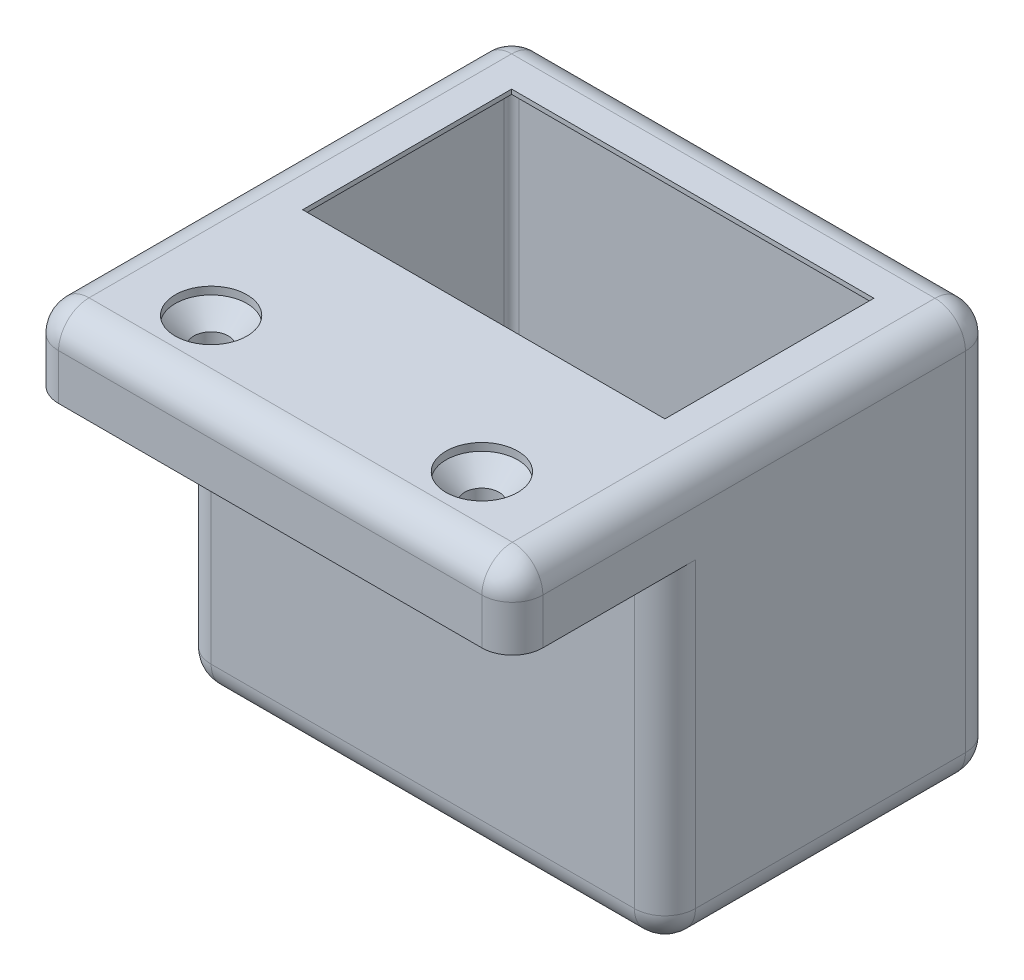
SolidWorks part; units mm, degrees
ref_plane "Front Plane" through (0, 0, 0) normal (0, 0, 1) x (1, 0, 0)
ref_plane "Top Plane" through (0, 0, 0) normal (0, 1, 0) x (1, 0, 0)
ref_plane "Right Plane" through (0, 0, 0) normal (1, 0, 0) x (0, 0, -1)
sketch "Profile Sketch" plane through (0, 0, 0) normal (1, 0, 0) x (0, 0, -1)
  line L0 (0, 0) -> (0, 43.6)
  line L1 (0, 43.6) -> (-20, 43.6)
  line L2 (-20, 43.6) -> (-20, 53.6)
  line L3 (-20, 53.6) -> (43.4, 53.6)
  line L4 (43.4, 53.6) -> (43.4, 0)
  line L5 (43.4, 0) -> (0, 0)
  dimension "D1" = 63.4
  dimension "D2" = 10
  dimension "D3" = 43.4
  dimension "D4" = 53.6
extrude "Profile Extrude" add sketch "Profile Sketch" along normal mid plane 63.5
sketch "Interior Sketch" plane through (0, 0, 0) normal (0, -1, 0) x (1, 0, 0)
  line L8 (-28.75, -3) -> (-28.75, -40.4)
  line L9 (-28.75, -40.4) -> (28.75, -40.4)
  line L10 (28.75, -40.4) -> (28.75, -3)
  line L11 (28.75, -3) -> (-28.75, -3)
  line L12 (-28.75, -3) -> (-28.75, -40.4)
  line L13 (-28.75, -40.4) -> (28.75, -40.4)
  line L14 (28.75, -40.4) -> (28.75, -3)
  line L15 (28.75, -3) -> (-28.75, -3)
  dimension "D1" = 3
extrude "Interior Cut" cut sketch "Interior Sketch" against normal offset from surface (50 mm away) 0.6 from offset 3 up to face at (0, 53.6, -11.7) offset against normal yes
sketch "Opening Sketch" plane through (0, 53.6, 0) normal (0, 1, 0) x (1, 0, 0)
  line L8 (-23.75, 8) -> (23.75, 8)
  line L9 (-23.75, 35.4) -> (-23.75, 8)
  line L10 (23.75, 35.4) -> (-23.75, 35.4)
  line L11 (23.75, 8) -> (23.75, 35.4)
  line L12 (-23.75, 8) -> (23.75, 8)
  line L13 (-23.75, 35.4) -> (-23.75, 8)
  line L14 (23.75, 35.4) -> (-23.75, 35.4)
  line L15 (23.75, 8) -> (23.75, 35.4)
  dimension "D1" = 5
extrude "Opening Cut" cut sketch "Opening Sketch" against normal up to next
chamfer "Inside Top Chamfer" distance 5 angle 45 4 edges at (28.75, 53, -21.7) (0, 53, -40.4) (-28.75, 53, -21.7) (0, 53, -3)
fillet "Inside Fillets" radius 1 4 edges at (-28.75, 25.5, -3) (28.75, 25.5, -3) (28.75, 25.5, -40.4) (-28.75, 25.5, -40.4)
sketch "Wire Outlet Cut Sketch" plane through (0, 0, 0) normal (0, -1, 0) x (1, 0, 0)
  line L0 (-31.75, -43.4) -> (31.75, 0) construction
  circle A0 centre (0, -21.7) radius 9.5
  dimension "D1" = 19
extrude "Wire Outlet Cut" cut sketch "Wire Outlet Cut Sketch" against normal up to next
fillet "Wire Outlet Fillet" 2 edges at (0, 0, -31.2) (0, 3, -31.2) type full round first side face at (0, 0, -31.2) second side face at (0, 3, -31.2) middle face at (0, 0, -31.2)
fillet "Top Fillets" radius 4 14 edges at (0, 0, 0) (31.75, 0, -21.7) (0, 0, -43.4) (-31.75, 0, -21.7) (-31.75, 26.8, -43.4) (0, 53.6, -43.4) (31.75, 26.8, -43.4) (-31.75, 21.8, 0) (31.75, 21.8, 0) (-31.75, 53.6, -11.7) (-31.75, 48.6, 20) (0, 53.6, 20) (31.75, 53.6, -11.7) (31.75, 48.6, 20)
sketch "Mounting Hole Layout Sketch" plane through (0, 53.6, 0) normal (0, 1, 0) x (1, 0, 0)
  line L0 (0, 0) -> (0, -27.8287) construction
  line L1 (27.75, -20) -> (-27.75, -20) construction
  point P3 (-17.75, -10)
  point P4 (17.75, -10)
  dimension "D1" = 35.5
  dimension "D2" = 10
hole_wizard "M4 Mounting Screws" positions "M4 Mounting Screws Position Sketch" profile "M4 Mounting Screws Profile Sketch" countersink size "M4" standard "ANSI Metric" end condition up to next
sketch3d "M4 Mounting Screws Position Sketch"
  point P0 (-17.75, 53.6, 10)
  point P3 (17.75, 53.6, 10)
sketch "M4 Mounting Screws Profile Sketch" plane through (-17.75, 53.6, 10) normal (1, 0, 0) x (0, 0, 1)
  line L0 (0, 0) -> (0, 10)
  line L1 (0, 10) -> (2.25, 10)
  line L2 (2.25, 10) -> (2.25, 3.45)
  line L3 (2.25, 3.45) -> (4.7, 1)
  line L4 (4.7, 1) -> (4.7, 0)
  line L6 (4.7, 0) -> (0, 0)
  line L7 (-2.25, 3.45) -> (-4.7, 1) construction
  line L11 (0, -6.35) -> (0, 107.95) construction
  dimension "Thru Hole Dia." = 4.5
  dimension "Thru Hole Depth" = 10
  dimension "C'Sink Dia." = 9.4
  dimension "C'Sink Angle" = 90
  dimension "Head Clearance" = 1
